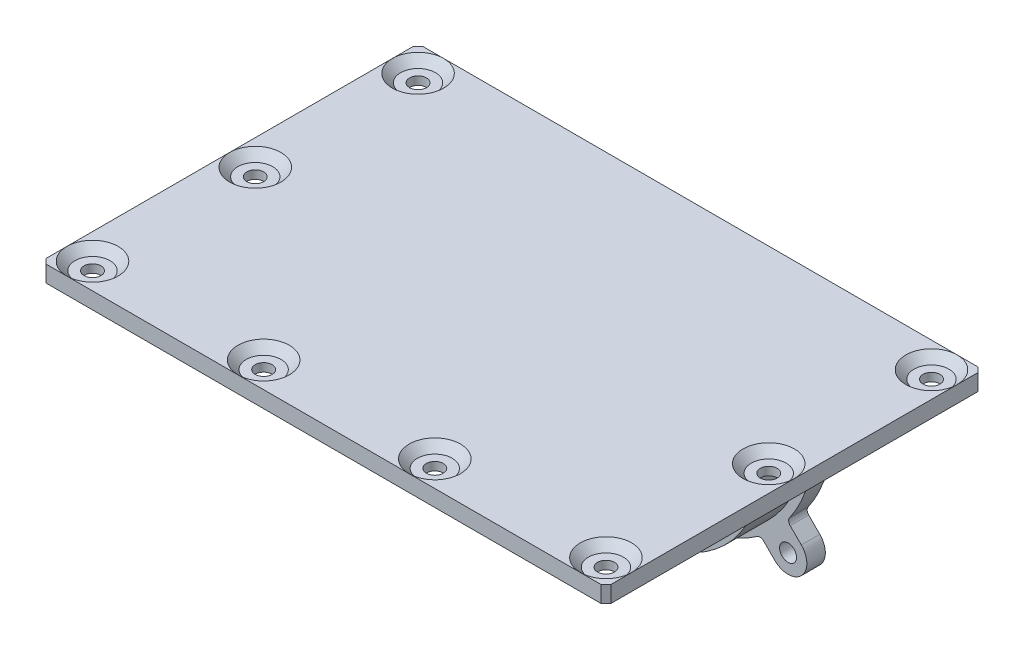
SolidWorks part; units mm, degrees
ref_plane "Front Plane" through (0, 0, 0) normal (0, 0, 1) x (1, 0, 0)
ref_plane "Top Plane" through (0, 0, 0) normal (0, 1, 0) x (1, 0, 0)
ref_plane "Right Plane" through (0, 0, 0) normal (1, 0, 0) x (0, 0, -1)
sketch "Sketch1" plane through (0, 0, 0) normal (0, 0, 1) x (1, 0, 0)
  line L14 (-25.56, 0) -> (-25.56, 14.03)
  line L29 (25.56, 0) -> (25.56, 14.03)
  line L31 (18.0736, -23.2497) -> (15.9014, -21.0774)
  line L37 (23.2497, -18.0736) -> (21.0774, -15.9014)
  line L38 (-23.2497, -18.0736) -> (-21.0774, -15.9014)
  line L39 (-18.0736, -23.2497) -> (-15.9014, -21.0774)
  line L40 (-55, 25.56) -> (-55, 22.35)
  line L41 (-32.88, 18.69) -> (-32.88, 21.35)
  line L42 (55, 22.35) -> (33.88, 22.35)
  line L43 (-29.22, 15.03) -> (-26.56, 15.03)
  line L44 (55, 25.56) -> (-55, 25.56)
  line L45 (55, 25.56) -> (55, 22.35)
  line L46 (32.88, 18.69) -> (32.88, 21.35)
  line L47 (26.56, 15.03) -> (29.22, 15.03)
  line L48 (-55, 22.35) -> (-33.88, 22.35)
  circle A0 centre (0, 0) radius 22.35
  arc A44 (-25.56, 0) -> (-20.9643, -14.6222) centre (0, 0) ccw
  arc A45 (-23.2497, -18.0736) -> (-18.0736, -23.2497) centre (-20.6617, -20.6617) ccw
  arc A46 (18.0736, -23.2497) -> (23.2497, -18.0736) centre (20.6617, -20.6617) ccw
  circle A47 centre (-20.6617, -20.6617) radius 1.65
  circle A48 centre (20.6617, -20.6617) radius 1.65
  arc A49 (-32.88, 18.69) -> (-29.22, 15.03) centre (-29.22, 18.69) ccw
  arc A50 (29.22, 15.03) -> (32.88, 18.69) centre (29.22, 18.69) ccw
  circle A51 centre (29.22, 18.69) radius 1.65
  circle A52 centre (-29.22, 18.69) radius 1.65
  arc A53 (-14.6222, -20.9643) -> (14.6222, -20.9643) centre (0, 0) ccw
  arc A54 (20.9643, -14.6222) -> (25.56, 0) centre (0, 0) ccw
  arc A55 (32.88, 21.35) -> (33.88, 22.35) centre (33.88, 21.35) cw
  arc A56 (26.56, 15.03) -> (25.56, 14.03) centre (26.56, 14.03) ccw
  arc A57 (21.0774, -15.9014) -> (20.9643, -14.6222) centre (21.7845, -15.1943) cw
  arc A58 (15.9014, -21.0774) -> (14.6222, -20.9643) centre (15.1943, -21.7845) ccw
  arc A59 (-15.9014, -21.0774) -> (-14.6222, -20.9643) centre (-15.1943, -21.7845) cw
  arc A60 (-21.0774, -15.9014) -> (-20.9643, -14.6222) centre (-21.7845, -15.1943) ccw
  arc A61 (-26.56, 15.03) -> (-25.56, 14.03) centre (-26.56, 14.03) cw
  arc A62 (-32.88, 21.35) -> (-33.88, 22.35) centre (-33.88, 21.35) ccw
extrude "Boss-Extrude1" add sketch "Sketch1" along normal blind 73.4
sketch "Sketch2" plane through (0, 0, 73.4) normal (0, 0, 1) x (1, 0, 0)
  line L15 (-25.56, 0) -> (-25.56, 14.03)
  line L16 (25.56, 0) -> (25.56, 14.03)
  line L17 (18.0736, -23.2497) -> (15.9014, -21.0774)
  line L18 (23.2497, -18.0736) -> (21.0774, -15.9014)
  line L19 (-23.2497, -18.0736) -> (-21.0774, -15.9014)
  line L20 (-18.0736, -23.2497) -> (-15.9014, -21.0774)
  line L21 (-32.88, 18.69) -> (-32.88, 21.35)
  line L22 (-29.22, 15.03) -> (-26.56, 15.03)
  line L23 (32.88, 18.69) -> (32.88, 21.35)
  line L24 (26.56, 15.03) -> (29.22, 15.03)
  line L25 (-33.88, 22.35) -> (33.88, 22.35)
  arc A29 (-25.56, 0) -> (-20.9643, -14.6222) centre (0, 0) ccw
  arc A30 (-23.2497, -18.0736) -> (-18.0736, -23.2497) centre (-20.6617, -20.6617) ccw
  arc A31 (18.0736, -23.2497) -> (23.2497, -18.0736) centre (20.6617, -20.6617) ccw
  arc A34 (-32.88, 18.69) -> (-29.22, 15.03) centre (-29.22, 18.69) ccw
  arc A35 (29.22, 15.03) -> (32.88, 18.69) centre (29.22, 18.69) ccw
  arc A38 (-14.6222, -20.9643) -> (14.6222, -20.9643) centre (0, 0) ccw
  arc A39 (20.9643, -14.6222) -> (25.56, 0) centre (0, 0) ccw
  arc A40 (32.88, 21.35) -> (33.88, 22.35) centre (33.88, 21.35) cw
  arc A41 (26.56, 15.03) -> (25.56, 14.03) centre (26.56, 14.03) ccw
  arc A42 (21.0774, -15.9014) -> (20.9643, -14.6222) centre (21.7845, -15.1943) cw
  arc A43 (15.9014, -21.0774) -> (14.6222, -20.9643) centre (15.1943, -21.7845) ccw
  arc A44 (-15.9014, -21.0774) -> (-14.6222, -20.9643) centre (-15.1943, -21.7845) cw
  arc A45 (-21.0774, -15.9014) -> (-20.9643, -14.6222) centre (-21.7845, -15.1943) ccw
  arc A46 (-26.56, 15.03) -> (-25.56, 14.03) centre (-26.56, 14.03) cw
  arc A47 (-32.88, 21.35) -> (-33.88, 22.35) centre (-33.88, 21.35) ccw
extrude "Cut-Extrude1" cut sketch "Sketch2" against normal offset from surface (69.8 mm away) 3.6 up to face at (30.87, 18.69, 0)
sketch "Sketch3" plane through (0, 25.56, 0) normal (0, 1, 0) x (1, 0, 0)
  line L1 (-54.0569, -73.4) -> (-55, -72.4569)
  line L5 (54.0569, -73.4) -> (55, -72.4569)
  line L6 (-55, -0.9431) -> (-54.0569, 0)
  line L7 (55, -0.9431) -> (54.0569, 0)
  line L17 (-54.0569, 0) -> (-55, 0)
  line L18 (-55, -0.9431) -> (-55, 0)
  line L19 (-54.0569, -73.4) -> (-55, -73.4)
  line L20 (-55, -72.4569) -> (-55, -73.4)
  line L21 (54.0569, -73.4) -> (55, -73.4)
  line L22 (55, -72.4569) -> (55, -73.4)
  line L23 (55, -0.9431) -> (55, 0)
  line L24 (55, 0) -> (54.0569, 0)
  circle A14 centre (50, -68.4) radius 1.65
  circle A15 centre (50, -5) radius 1.65
  circle A16 centre (-50, -5) radius 1.65
  circle A17 centre (-50, -68.4) radius 1.65
  circle A18 centre (16.6667, -68.4) radius 1.65
  circle A19 centre (-16.6667, -68.4) radius 1.65
  circle A20 centre (-50, -36.7) radius 1.65
  circle A21 centre (50, -36.7) radius 1.65
extrude "Cut-Extrude2" cut sketch "Sketch3" against normal up to surface (3.21 mm away) up to face at (0, 22.35, 17.5111)
sketch "Sketch4" plane through (0, 0, 3.6) normal (0, 0, 1) x (1, 0, 0)
  line L3 (-12.7632, 22.45) -> (12.7632, 22.45)
  circle A0 centre (0, 0) radius 22.35
  arc A4 (-12.2518, 20.5906) -> (12.2518, 20.5906) centre (0, 0) ccw
  arc A5 (12.2518, 20.5906) -> (12.7632, 22.45) centre (12.7632, 21.45) cw
  arc A6 (-12.2518, 20.5906) -> (-12.7632, 22.45) centre (-12.7632, 21.45) ccw
extrude "Boss-Extrude2" add sketch "Sketch4" along normal blind 2.4
sketch "Sketch6" plane through (0, 0, 6) normal (0, 0, 1) x (1, 0, 0)
  line L0 (-12.7632, 22.45) -> (12.7632, 22.45)
  circle A0 centre (0, 0) radius 21.6
  arc A4 (-12.2518, 20.5906) -> (12.2518, 20.5906) centre (0, 0) ccw
  arc A5 (12.2518, 20.5906) -> (12.7632, 22.45) centre (12.7632, 21.45) cw
  arc A6 (-12.2518, 20.5906) -> (-12.7632, 22.45) centre (-12.7632, 21.45) ccw
extrude "Boss-Extrude3" add sketch "Sketch6" along normal blind 6
chamfer "Chamfer1" distance 0.75 angle 45 1 edges at (21.6, 0, 6)
sketch "Sketch7" plane through (0, 25.56, 0) normal (0, 1, 0) x (1, 0, 0)
  circle A0 centre (50, -68.4) radius 3.4
  circle A1 centre (16.6667, -68.4) radius 3.4
  circle A2 centre (-16.6667, -68.4) radius 3.4
  circle A3 centre (-50, -68.4) radius 3.4
  circle A4 centre (50, -36.7) radius 3.4
  circle A5 centre (50, -5) radius 3.4
  circle A6 centre (-50, -36.7) radius 3.4
  circle A7 centre (-50, -5) radius 3.4
extrude "Cut-Extrude3" cut sketch "Sketch7" against normal blind 1.6
chamfer "Chamfer2" distance 1.6 angle 45 8 edges at (46.6, 25.56, 5) (46.6, 25.56, 36.7) (46.6, 25.56, 68.4) (13.2667, 25.56, 68.4) (-20.0667, 25.56, 68.4) (-53.4, 25.56, 68.4) (-53.4, 25.56, 36.7) (-53.4, 25.56, 5)
